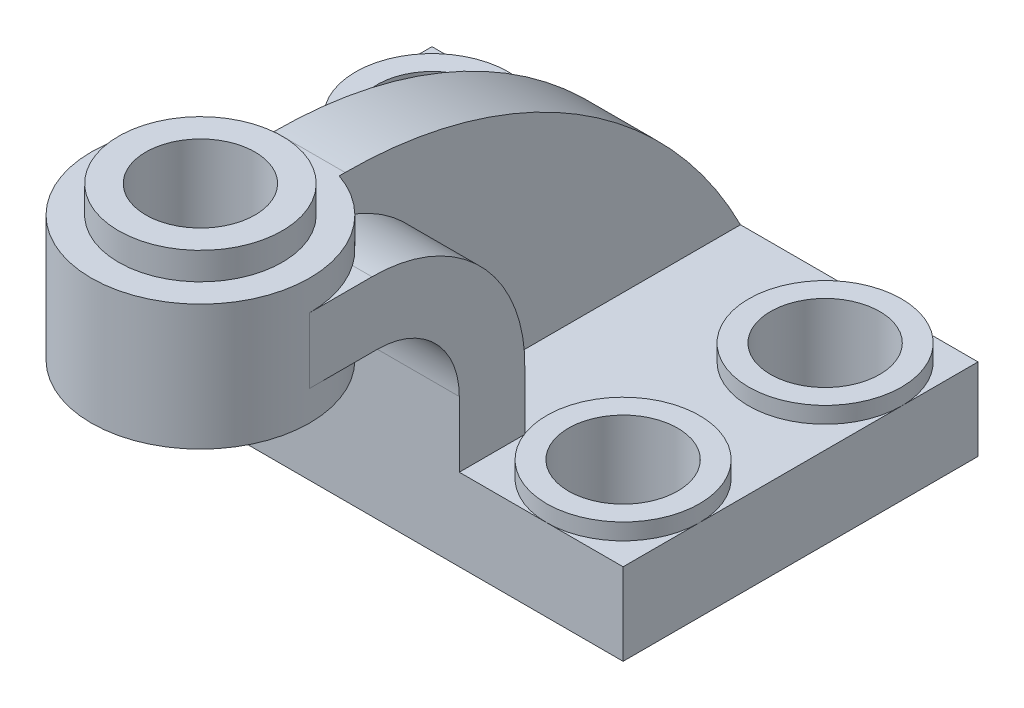
SolidWorks part; units mm, degrees
ref_plane "Front Plane" through (0, 0, 0) normal (0, 0, 1) x (1, 0, 0)
ref_plane "Top Plane" through (0, 0, 0) normal (0, 1, 0) x (1, 0, 0)
ref_plane "Right Plane" through (0, 0, 0) normal (1, 0, 0) x (0, 0, -1)
sketch "Sketch1" plane through (0, 0, 0) normal (0, 1, 0) x (1, 0, 0)
  line L0 (-35.3618, -30.1745) -> (-35.3618, 34.8255)
  line L2 (64.6382, 34.8255) -> (64.6382, -30.1745)
  line L3 (64.6382, -30.1745) -> (-35.3618, -30.1745)
  line L4 (-35.3618, 34.8255) -> (64.6382, 34.8255)
  circle A2 centre (50.6382, 20.8255) radius 14
  circle A3 centre (50.6382, 20.8255) radius 10
  circle A4 centre (50.6382, -16.1745) radius 14
  circle A5 centre (50.6382, -16.1745) radius 10
  circle A6 centre (-21.3618, 20.8255) radius 10
  circle A7 centre (-21.3618, 20.8255) radius 14
  circle A8 centre (-21.3618, -16.1745) radius 14
  circle A9 centre (-21.3618, -16.1745) radius 10
  dimension "D3" = 28
  dimension "D4" = 28
  dimension "D5" = 20
  dimension "D6" = 28
  dimension "D7" = 20
  dimension "D8" = 28
  dimension "D9" = 20
  dimension "D1" = 100
  dimension "D2" = 65
extrude "Boss-Extrude2" add sketch "Sketch1" along normal blind 3 contours A9 | A8 A9 | A4 A5 | A2 A3 | A7 A6
sketch "Sketch2" plane through (0, 0, 0) normal (0, 1, 0) x (1, 0, 0)
  line L0 (-35.3618, -30.1745) -> (-35.3618, 34.8255)
  line L1 (-35.3618, 34.8255) -> (64.6382, 34.8255)
  line L2 (64.6382, 34.8255) -> (64.6382, -30.1745)
  line L3 (64.6382, -30.1745) -> (-35.3618, -30.1745)
  circle A0 centre (50.6382, 20.8255) radius 14 construction
  point P3 (0, 0)
  dimension "D1" = 100
  dimension "D2" = 65
extrude "Boss-Extrude3" add sketch "Sketch2" against normal blind 15
ref_plane "Plane1" through (14.6382, 0, 0) normal (1, 0, 0) x (0, 0, -1)
sketch "Sketch3" plane through (14.6382, 0, 0) normal (1, 0, 0) x (0, 0, -1)
  line L0 (-30.1745, 0) -> (-30.1745, 12)
  line L1 (-45.1745, 27) -> (-57.5871, 27)
  line L2 (-18.1745, -1.4779) -> (-18.1745, 10.5221)
  line L3 (-46.1704, 39) -> (-57.5871, 39)
  line L4 (-30.1745, 0) -> (-18.1745, 0)
  line L6 (-30.1745, -15) -> (34.8255, -15) construction
  line L7 (-57.5871, 39) -> (-57.5871, 27)
  arc A0 (-30.1745, 12) -> (-45.1745, 27) centre (-45.1745, 12) ccw
  arc A1 (-46.1704, 39) -> (-18.1745, 10.5221) centre (-46.1704, 11) cw
  dimension "D1" = 15
  dimension "D3" = 28
  dimension "D2" = 12
  dimension "D4" = 12
  dimension "D5" = 54
extrude "Boss-Extrude4" add sketch "Sketch3" along normal mid plane 40 contours A1 L3 L7 L1 A0 L0 L4 L2
sketch "Sketch4" plane through (0, 39, 0) normal (0, 1, 0) x (1, 0, 0)
  line L0 (34.6382, -57.5871) -> (-5.3618, -57.5871) construction
  circle A0 centre (14.6382, -57.5871) radius 20
extrude "Boss-Extrude5" add sketch "Sketch4" along normal blind 5.5
sketch "Sketch5" plane through (0, 44.5, 0) normal (0, 1, 0) x (1, 0, 0)
  circle A0 centre (14.6382, -57.5871) radius 20
extrude "Boss-Extrude6" add sketch "Sketch5" against normal blind 23
sketch "Sketch6" plane through (0, 44.5, 0) normal (0, 1, 0) x (1, 0, 0)
  circle A0 centre (14.6382, -57.5871) radius 15
extrude "Boss-Extrude7" add sketch "Sketch6" along normal blind 5
sketch "Sketch7" plane through (0, 49.5, 0) normal (0, 1, 0) x (1, 0, 0)
  circle A0 centre (14.6382, -57.5871) radius 10
extrude "Cut-Extrude1" cut sketch "Sketch7" against normal through all
sketch "Sketch12" plane through (14.6382, 0, 0) normal (1, 0, 0) x (0, 0, -1)
  line L0 (-37.5871, 44.5) -> (-77.5871, 44.5) construction
  line L1 (-77.5871, 21.5) -> (-37.5871, 21.5) construction
  line L2 (-18.1745, 3) -> (-18.1704, 11)
  line L3 (20.8255, 0) -> (34.8255, 0) construction
  line L4 (-37.5871, 44.5) -> (-42.0028, 44.5)
  line L5 (34.8255, 0) -> (31.6547, 0)
  line L6 (-18.1745, 0) -> (-18.1745, 10.5221) construction
  line L7 (-6.1745, 3) -> (-26.1745, 3) construction
  line L8 (34.8255, 0) -> (-30.1745, 0)
  line L9 (-30.1745, 0) -> (-16.1745, 0) construction
  line L11 (34.8255, 0) -> (-18.1745, 0)
  line L12 (-18.1745, 3) -> (-18.1745, 0)
  line L13 (-42.0028, 44.5) -> (-42.0028, 38.6881)
  arc A0 (-37.5871, 44.5) -> (34.8255, 0) centre (-37.5871, -36.6666) cw
  arc A2 (-18.1745, 10.5221) -> (-46.1704, 39) centre (-46.1704, 11) ccw construction
  arc A3 (-18.1704, 11) -> (-37.5871, 37.6519) centre (-46.1508, 11.0143) ccw
  arc A4 (-42.0028, 38.6881) -> (-37.5871, 37.6519) centre (-46.2109, 10.8273) cw
  dimension "D2" = 81.1666
  dimension "D1" = 23
extrude "Boss-Extrude8" add sketch "Sketch12" along normal mid plane 13 contours L13 A4 A3 L2 L12 L8 L5 A0 L4
sketch "Sketch13" plane through (0, 0, 0) normal (0, 1, 0) x (1, 0, 0)
  circle A0 centre (-21.3618, 20.8255) radius 10
  circle A1 centre (-21.3618, -16.1745) radius 10
  circle A2 centre (50.6382, 20.8255) radius 10
  circle A3 centre (50.6382, -16.1745) radius 10
extrude "Cut-Extrude2" cut sketch "Sketch13" against normal through all
